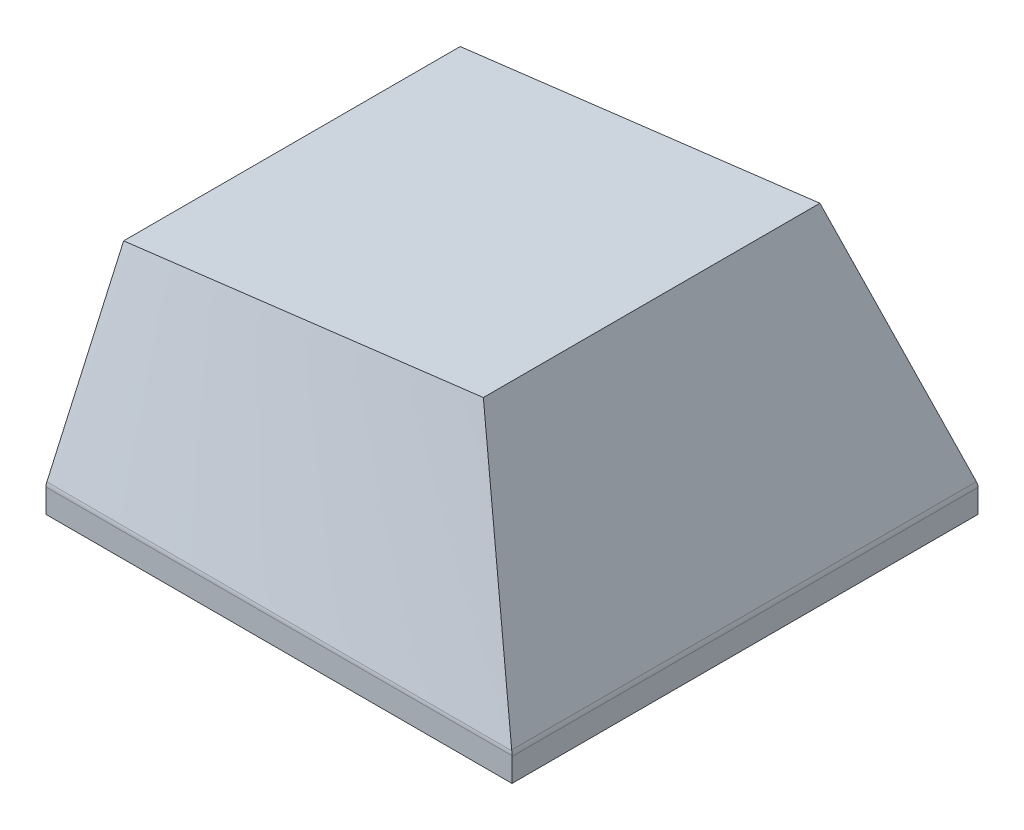
SolidWorks part; units mm, degrees
material "ABS"
ref_plane "Front Plane" through (0, 0, 0) normal (0, 0, 1) x (1, 0, 0)
ref_plane "Top Plane" through (0, 0, 0) normal (0, 1, 0) x (1, 0, 0)
ref_plane "Right Plane" through (0, 0, 0) normal (1, 0, 0) x (0, 0, -1)
sketch "Sketch1" plane through (0, 0, 0) normal (0, 1, 0) x (1, 0, 0)
  line L1 (-9, 9) -> (9, 9)
  line L2 (-9, 9) -> (-9, -9)
  line L3 (-9, -9) -> (9, -9)
  line L4 (9, 9) -> (9, -9)
  line L5 (-9, 9) -> (9, -9) construction
  line L6 (-9, -9) -> (9, 9) construction
  point P0 (0, 0)
  dimension "D1" = 18
  dimension "D2" = 18
ref_plane "Plane2" through (0, 9.3, 0) normal (0, 1, 0) x (1, 0, 0)
sketch "Sketch3" plane through (0, 9.3, 0) normal (0, 1, 0) x (1, 0, 0)
  line L0 (9, 9) -> (9, -9) construction
  line L1 (9, -9) -> (-9, -9) construction
  line L2 (-9, -9) -> (-9, 9) construction
  line L3 (-9, 9) -> (9, 9) construction
ref_plane "Plane3" through (-0.9913, 8.0732, 0) normal (0.1219, -0.9925, 0) x (0, 0, 1)
sketch "Sketch5" plane through (-0.9913, 8.0732, 0) normal (0.1219, -0.9925, 0) x (0, 0, 1)
  line L0 (0, 14.7768) -> (0, -15.9558) construction
  line L1 (-6.5, 7.5671) -> (6.5, 7.5671)
  line L2 (-6.5, 7.5671) -> (-6.5, -6.4329)
  line L3 (-6.5, -6.4329) -> (6.5, -6.4329)
  line L4 (6.5, 7.5671) -> (6.5, -6.4329)
  line L6 (-9, -8.9329) -> (9, -8.9329) construction
  point P5 (0, -6.4329)
  dimension "D1" = 13
  dimension "D2" = 14
  dimension "D3" = 2.5
loft "Loft1" add profiles "Sketch1", "Sketch5" connector at (-9, 0, 9) connector at (-8.5019, 7.151, 6.5)
sketch "Sketch6" plane through (0, 0, 0) normal (0, 0, 1) x (1, 0, 0)
  line L1 (-9, 0) -> (9, 0)
  line L2 (-9, 0) -> (-9, -1)
  line L3 (-9, -1) -> (9, -1)
  line L4 (9, 0) -> (9, -1)
  dimension "D1" = 1
extrude "Boss-Extrude1" add sketch "Sketch6" along normal mid plane 18
ref_plane "Plane4" through (-0.9913, 8.0732, 0) normal (-0.1219, 0.9925, 0) x (0.9925, 0.1219, 0)
ref_plane "Plane5" through (6.385, 0.784, 0) normal (-0.9925, -0.1219, 0) x (0, 0, 1)
sketch "Sketch7" plane through (6.385, 0.784, 0) normal (-0.9925, -0.1219, 0) x (0, 0, 1)
  line L0 (6.5, 8.1339) -> (-6.5, 8.1339)
  arc A0 (6.5, 8.1339) -> (-6.5, 8.1339) centre (0, 37.9227) cw
shell "Shell1" thickness 1.25 removed face at (0, -1, 0)
sketch "Sketch11" plane through (0, -1, 0) normal (0, -1, 0) x (1, 0, 0)
  circle A0 centre (0, 0) radius 2.8
  dimension "D1" = 5.6
fillet "Fillet5" radius 0.5 4 edges
